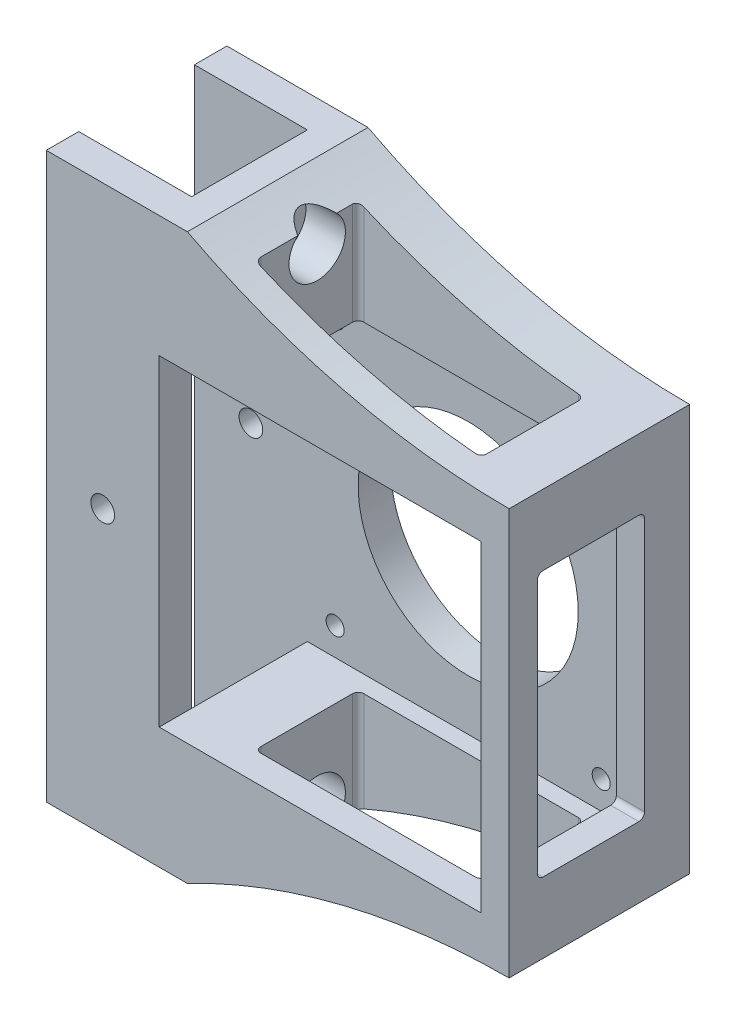
SolidWorks part; units mm, degrees
material "PBT Общее назначение"
ref_plane "Спереди" through (0, 0, 0) normal (0, 0, 1) x (1, 0, 0)
ref_plane "Сверху" through (0, 0, 0) normal (0, 1, 0) x (1, 0, 0)
ref_plane "Справа" through (0, 0, 0) normal (1, 0, 0) x (0, 0, -1)
sketch "Эскиз1" plane through (0, 0, 0) normal (0, 0, 1) x (1, 0, 0)
  line L0 (0, -50) -> (0, 50)
  line L1 (0, 50) -> (25, 50)
  line L2 (0, -50) -> (25, -50)
  line L3 (82, 36) -> (0, 36) construction
  line L4 (82, 36) -> (82, -36)
  line L5 (0, 0) -> (82, 0) construction
  arc A0 (25, 50) -> (82, 36) centre (82, 159.0357) ccw
  arc A1 (25, -50) -> (82, -36) centre (82, -159.0357) cw
  dimension "D1" = 50
  dimension "D2" = 82
  dimension "D3" = 25
  dimension "D4" = 36
  dimension "D5" = 57
extrude "Бобышка-Вытянуть1" add sketch "Эскиз1" along normal blind 52
sketch "Эскиз2" plane through (0, 0, 52) normal (0, 0, 1) x (1, 0, 0)
  line L0 (82, 0) -> (-10.2579, 0) construction
  line L1 (82, -36) -> (82, 36) construction
  line L2 (77, 28.5) -> (77, -28.5)
  line L3 (77, 28.5) -> (20, 28.5)
  line L4 (77, -28.5) -> (20, -28.5)
  line L5 (20, 28.5) -> (20, -28.5)
  line L6 (82, 0) -> (20, 0) construction
  line L7 (0, 50) -> (0, -50) construction
  dimension "D1" = 57
  dimension "D2" = 20
  dimension "D3" = 57
extrude "Вырез-Вытянуть1" cut sketch "Эскиз2" against normal through all
sketch "Эскиз3" plane through (0, 0, 0) normal (-1, 0, 0) x (0, 0, 1)
  line L0 (26, 50) -> (26, -50) construction
  line L1 (52, 50) -> (0, 50) construction
  line L2 (52, -50) -> (0, -50) construction
  line L3 (15.75, 50) -> (36.25, 50)
  line L4 (15.75, 50) -> (15.75, -50)
  line L5 (36.25, 50) -> (36.25, -50)
  line L6 (15.75, -50) -> (36.25, -50)
  line L7 (26, -50) -> (26, 50) construction
  dimension "D1" = 20.5
extrude "Вырез-Вытянуть2" cut sketch "Эскиз3" against normal blind 20
sketch "Эскиз4" plane through (0, 0, 0) normal (0, 0, -1) x (-1, 0, 0)
  line L4 (0, 50) -> (-25, 50)
  line L5 (-82, 36) -> (-82, -36)
  line L6 (-25, -50) -> (0, -50)
  line L7 (0, -50) -> (0, 50)
  line L8 (0, 50) -> (-25, 50)
  line L9 (-82, 36) -> (-82, -36)
  line L10 (-25, -50) -> (0, -50)
  line L11 (0, -50) -> (0, 50)
  arc A2 (-82, 36) -> (-25, 50) centre (-82, 159.0357) ccw
  arc A3 (-25, -50) -> (-82, -36) centre (-82, -159.0357) ccw
  arc A4 (-82, 36) -> (-25, 50) centre (-82, 159.0357) ccw
  arc A5 (-25, -50) -> (-82, -36) centre (-82, -159.0357) ccw
  dimension "D1" = 0
extrude "Вырез-Вытянуть3" cut sketch "Эскиз4" against normal blind 10
sketch "Эскиз5" plane through (0, 0, 52) normal (0, 0, 1) x (1, 0, 0)
  line L4 (25, 50) -> (0, 50)
  line L5 (0, 50) -> (0, -50)
  line L6 (0, -50) -> (25, -50)
  line L7 (82, -36) -> (82, 36)
  line L8 (25, 50) -> (0, 50)
  line L9 (0, 50) -> (0, -50)
  line L10 (0, -50) -> (25, -50)
  line L11 (82, -36) -> (82, 36)
  arc A2 (82, -36) -> (25, -50) centre (82, -159.0357) ccw
  arc A3 (25, 50) -> (82, 36) centre (82, 159.0357) ccw
  arc A4 (82, -36) -> (25, -50) centre (82, -159.0357) ccw
  arc A5 (25, 50) -> (82, 36) centre (82, 159.0357) ccw
  dimension "D1" = 0
extrude "Вырез-Вытянуть4" cut sketch "Эскиз5" against normal blind 10
sketch "Эскиз6" plane through (0, 0, 10) normal (0, 0, -1) x (-1, 0, 0)
  line L0 (-20, -28.5) -> (-77, -28.5) construction
  line L1 (-20, 28.5) -> (-20, -28.5) construction
  line L2 (-77, 28.5) -> (-20, 28.5) construction
  line L3 (-77, -28.5) -> (-77, 28.5) construction
  line L4 (-20, -28.5) -> (-77, -28.5)
  line L5 (-20, 28.5) -> (-20, -28.5)
  line L6 (-77, 28.5) -> (-20, 28.5)
  line L7 (-77, -28.5) -> (-77, 28.5)
extrude "Бобышка-Вытянуть2" add sketch "Эскиз6" against normal up to surface (5.75 mm away) up to face at (13.3333, 0, 15.75)
sketch "Эскиз7" plane through (0, 0, 15.75) normal (0, 0, 1) x (1, 0, 0)
  line L0 (20, -28.5) -> (20, 28.5) construction
  line L1 (77, -28.5) -> (20, -28.5) construction
  line L2 (77, 28.5) -> (77, -28.5) construction
  line L3 (20, 28.5) -> (77, 28.5) construction
  line L4 (20, -28.5) -> (20, 28.5) construction
  line L5 (77, -28.5) -> (20, -28.5) construction
  line L6 (77, 28.5) -> (77, -28.5) construction
  line L7 (20, 28.5) -> (77, 28.5) construction
  line L8 (48.5, -28.5) -> (48.5, 28.5) construction
  line L9 (20, 0) -> (77, 0) construction
  circle A0 centre (48.5, 0) radius 19.5
  dimension "D1" = 39
extrude "Вырез-Вытянуть5" cut sketch "Эскиз7" against normal through all
sketch "Эскиз8" plane through (20, 0, 0) normal (-1, 0, 0) x (0, 0, 1)
  line L0 (42, -36) -> (10, -36) construction
  line L1 (36.25, -36) -> (15.75, -36) construction
  line L2 (15.75, -50) -> (36.25, -50) construction
  line L3 (15.75, -50) -> (36.25, -50) construction
  line L4 (15.75, -28.5) -> (15.75, -50) construction
  line L5 (36.25, -50) -> (36.25, -28.5) construction
  line L6 (15.75, -36) -> (15.75, -50) construction
  line L7 (36.25, -50) -> (36.25, -36) construction
  line L8 (26, -50) -> (26, -36) construction
  line L9 (36.25, -43) -> (15.75, -43) construction
  line L10 (36.25, 50) -> (15.75, 50) construction
  line L12 (15.75, 50) -> (15.75, 28.5) construction
  line L13 (36.25, 28.5) -> (36.25, 50) construction
  line L14 (36.25, 50) -> (15.75, 50) construction
  line L15 (26, 36) -> (26, 50) construction
  line L16 (15.75, 50) -> (15.75, 36) construction
  line L17 (36.25, 36) -> (36.25, 50) construction
  line L18 (42, 36) -> (10, 36) construction
  line L19 (36.25, 36) -> (15.75, 36) construction
  line L20 (15.75, 43) -> (36.25, 43) construction
  circle A0 centre (26, -43) radius 2.1
  circle A1 centre (26, 43) radius 2.1
  dimension "D1" = 4.2
  dimension "D2" = 4.2
extrude "Вырез-Вытянуть6" cut sketch "Эскиз8" against normal through all
sketch "Эскиз9" plane through (0, 0, 10) normal (0, 0, -1) x (-1, 0, 0)
  line L0 (-82, 0) -> (0, 0) construction
  line L1 (-82, 36) -> (-82, -36) construction
  line L2 (0, -50) -> (0, 50) construction
ref_plane "СимY" through (0, 0, 0) normal (0, -1, 0) x (-1, 0, 0)
ref_plane "Плоскость2" through (25, 0, 0) normal (-1, 0, 0) x (0, 0, 1)
sketch "Эскиз10" plane through (25, 0, 0) normal (-1, 0, 0) x (0, 0, 1)
  circle A0 centre (26, 43) radius 2.1 construction
  circle A1 centre (26, -43) radius 2.1 construction
  circle A2 centre (26, 43) radius 2.1 construction
  circle A3 centre (26, -43) radius 2.1 construction
  circle A4 centre (26, 43) radius 5
  circle A5 centre (26, -43) radius 5
  dimension "D1" = 10
  dimension "D2" = 10
extrude "Вырез-Вытянуть7" cut sketch "Эскиз10" against normal through all
sketch "Эскиз12" plane through (0, 0, 10) normal (0, 0, -1) x (-1, 0, 0)
  line L0 (-20, 50) -> (0, 50) construction
  line L1 (0, 50) -> (0, -50) construction
  line L2 (-20, -50) -> (0, -50) construction
  line L3 (-20, 50) -> (0, 50) construction
  line L4 (0, 50) -> (0, -50) construction
  line L5 (-20, -50) -> (0, -50) construction
  line L6 (-20, 50) -> (-20, 28.5) construction
  line L7 (-20, 50) -> (-20, -50) construction
  line L8 (-20, 0) -> (0, 0) construction
  line L9 (-10, 50) -> (-10, -50) construction
  circle A0 centre (-10, 0) radius 2.1
  dimension "D1" = 4.2
extrude "Вырез-Вытянуть8" cut sketch "Эскиз12" against normal through all
sketch "Эскиз13" plane through (82, 0, 0) normal (1, 0, 0) x (0, 0, -1)
  line L0 (-42, 0) -> (-10, 0) construction
  line L1 (-42, -36) -> (-42, 36) construction
  line L2 (-26, 0) -> (-26, -36.6008) construction
  line L3 (-42, -36) -> (-10, -36) construction
ref_plane "СимZ" through (0, 0, 26) normal (0, 0, 1) x (0, -1, 0)
sketch "Эскиз14" plane through (0, 0, 10) normal (0, 0, -1) x (-1, 0, 0)
  line L0 (-48.5, 0) -> (-48.5, 19.5) construction
  line L1 (-48.5, 0) -> (-29, 0) construction
  line L2 (-72.07, 23.57) -> (-24.93, 23.57) construction
  line L3 (-72.07, 23.57) -> (-72.07, -23.57) construction
  line L4 (-24.93, 23.57) -> (-24.93, -23.57) construction
  line L5 (-72.07, -23.57) -> (-24.93, -23.57) construction
  line L6 (-48.5, 23.57) -> (-48.5, -23.57) construction
  line L7 (-24.93, 0) -> (-72.07, 0) construction
  circle A0 centre (-48.5, 0) radius 19.5 construction
  circle A1 centre (-48.5, 0) radius 19.5 construction
  circle A2 centre (-72.07, 23.57) radius 1.6
  circle A3 centre (-24.93, 23.57) radius 1.6
  circle A4 centre (-24.93, -23.57) radius 1.6
  circle A5 centre (-72.07, -23.57) radius 1.6
  dimension "D3" = 3.2
  dimension "D4" = 3.2
  dimension "D5" = 3.2
  dimension "D6" = 3.2
  dimension "D1" = 47.14
  dimension "D2" = 47.14
extrude "Вырез-Вытянуть9" cut sketch "Эскиз14" against normal up to surface (5.75 mm away) up to face at (10, 2.1, 15.75)
sketch "Эскиз15" plane through (82, 0, 0) normal (1, 0, 0) x (0, 0, -1)
  line L0 (-37, 23.5) -> (-18, 23.5)
  line L1 (-37, 23.5) -> (-37, -23.5)
  line L2 (-18, 23.5) -> (-18, -23.5)
  line L3 (-37, -23.5) -> (-18, -23.5)
  line L5 (-42, -36) -> (-42, 36) construction
  line L6 (-10, 36) -> (-10, -36) construction
  line L7 (-15.75, -28.5) -> (-42, -28.5) construction
  line L8 (-15.75, -28.5) -> (-42, -28.5) construction
  line L9 (-15.75, 28.5) -> (-42, 28.5) construction
  line L10 (-15.75, 28.5) -> (-42, 28.5) construction
  dimension "D1" = 5
  dimension "D2" = 8
  dimension "D3" = 5
  dimension "D4" = 5
  dimension "D5" = 5
extrude "Вырез-Вытянуть10" cut sketch "Эскиз15" against normal up to surface (5 mm away) up to face at (77, 0, 28.875)
sketch "Sketch1" plane through (0, 28.5, 0) normal (0, -1, 0) x (1, 0, 0)
  line L0 (72, 37) -> (72, 18.75)
  line L1 (72, 37) -> (32, 37)
  line L2 (72, 18.75) -> (32, 18.75)
  line L3 (32, 37) -> (32, 18.75)
  line L4 (77, 15.75) -> (77, 42) construction
  line L5 (20, 42) -> (77, 42) construction
  line L6 (77, 15.75) -> (20, 15.75) construction
  dimension "D1" = 5
  dimension "D2" = 40
  dimension "D3" = 5
  dimension "D4" = 3
extrude "Cut-Extrude1" cut sketch "Sketch1" against normal through all and the other way through all
fillet "Скругление1" radius 1 4 edges at (79.5, -23.5, 18) (79.5, -23.5, 37) (79.5, 23.5, 37) (79.5, 23.5, 18)
fillet "Скругление2" radius 1 4 edges at (32, 37.5589, 18.75) (72, 32.4535, 18.75) (72, 32.4535, 37) (32, 37.5589, 37)
fillet "Скругление3" radius 1 4 edges at (72, -32.4535, 37) (32, -37.5589, 37) (32, -37.5589, 18.75) (72, -32.4535, 18.75)
sketch "Эскиз16" plane through (0, 0, 42) normal (0, 0, 1) x (1, 0, 0)
  line L0 (72, 36.4071) -> (72, 28.5) construction
  line L1 (72, 36.4071) -> (72, 28.5)
  line L2 (20, 28.5) -> (77, 28.5) construction
  line L3 (72, 28.5) -> (82, 28.5)
  line L4 (82, -36) -> (82, 36) construction
  line L5 (82, 28.5) -> (82, 36)
  arc A0 (25, 50) -> (82, 36) centre (82, 159.0357) ccw construction
  arc A1 (72, 36.4071) -> (82, 36) centre (82, 159.0357) ccw
extrude "Бобышка-Вытянуть3" add sketch "Эскиз16" against normal up to surface (32 mm away) up to face at (70.47, -23.57, 10)
sketch "Эскиз17" plane through (0, 0, 42) normal (0, 0, 1) x (1, 0, 0)
  line L0 (82, -36) -> (82, 36) construction
  line L1 (82, -36) -> (82, -28.5)
  line L2 (77, -28.5) -> (20, -28.5) construction
  line L3 (82, -28.5) -> (72, -28.5)
  line L4 (72, -28.5) -> (72, -36.4071) construction
  line L5 (72, -28.5) -> (72, -36.4071)
  arc A0 (82, -36) -> (25, -50) centre (82, -159.0357) ccw construction
  arc A1 (82, -36) -> (72, -36.4071) centre (82, -159.0357) ccw
extrude "Бобышка-Вытянуть4" add sketch "Эскиз17" against normal up to surface (32 mm away) up to face at (35.3843, 0, 10)
